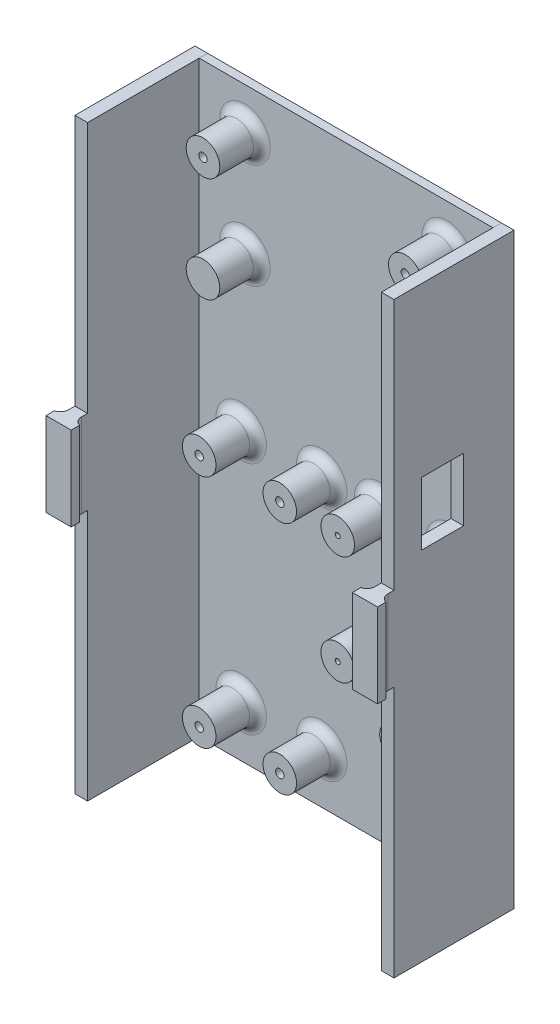
SolidWorks part; units mm, degrees
ref_plane "Přední rovina" through (0, 0, 0) normal (0, 0, 1) x (1, 0, 0)
ref_plane "Horní rovina" through (0, 0, 0) normal (0, 1, 0) x (1, 0, 0)
ref_plane "Pravá rovina" through (0, 0, 0) normal (1, 0, 0) x (0, 0, -1)
sketch "Skica1" plane through (0, 0, 0) normal (0, 0, 1) x (1, 0, 0)
  line L1 (0, 0) -> (70, 0)
  line L2 (0, 0) -> (0, 140)
  line L3 (0, 140) -> (70, 140)
  line L4 (70, 0) -> (70, 140)
  dimension "D1" = 140
  dimension "D2" = 70
extrude "Přidat vysunutím1" add sketch "Skica1" along normal blind 2
sketch "Skica2" plane through (0, 0, 2) normal (0, 0, 1) x (1, 0, 0)
  line L1 (70, 140) -> (0, 140) construction
  line L5 (0, 140) -> (0, 0) construction
  line L9 (70, 0) -> (70, 140) construction
  line L10 (0, 0) -> (70, 0) construction
  circle A0 centre (59.1, 130) radius 1
  circle A1 centre (10.9, 130) radius 1
  circle A2 centre (10, 68) radius 1
  circle A3 centre (29.2, 68) radius 1
  circle A4 centre (10, 12) radius 1
  circle A5 centre (29.2, 12) radius 1
  circle A6 centre (43, 68) radius 0.6
  circle A7 centre (60, 68) radius 0.6
  circle A8 centre (60, 42) radius 0.6
  circle A9 centre (55, 30) radius 0.6
  circle A10 centre (10, 68) radius 4
  circle A11 centre (29.2, 68) radius 4
  circle A12 centre (43, 68) radius 4
  circle A13 centre (60, 68) radius 4
  circle A14 centre (60, 42) radius 4
  circle A15 centre (55, 30) radius 4
  circle A16 centre (29.2, 12) radius 4
  circle A17 centre (10, 12) radius 4
  circle A18 centre (10.9, 130) radius 4
  circle A19 centre (59.1, 130) radius 4
  circle A20 centre (43, 42) radius 0.6
  circle A21 centre (43, 42) radius 4
  circle A22 centre (10.9, 105) radius 4
  circle A23 centre (59.1, 105) radius 4
  circle A24 centre (60, 14) radius 4
  dimension "D1" = 2
  dimension "D2" = 2
  dimension "D3" = 48.2
  dimension "D5" = 10.9
  dimension "D6" = 10
  dimension "D7" = 2
  dimension "D8" = 2
  dimension "D9" = 1.2
  dimension "D10" = 1.2
  dimension "D11" = 1.2
  dimension "D12" = 2
  dimension "D13" = 2
  dimension "D14" = 56
  dimension "D15" = 56
  dimension "D16" = 10
  dimension "D17" = 62
  dimension "D18" = 19.2
  dimension "D19" = 19.2
  dimension "D20" = 10
  dimension "D21" = 12
  dimension "D22" = 26
  dimension "D23" = 0
  dimension "D24" = 17
  dimension "D25" = 10
  dimension "D26" = 62
  dimension "D27" = 42
  dimension "D28" = 30
  dimension "D29" = 1.2
  dimension "D30" = 15
  dimension "D31" = 8
  dimension "D32" = 8
  dimension "D33" = 8
  dimension "D34" = 8
  dimension "D35" = 8
  dimension "D36" = 8
  dimension "D37" = 8
  dimension "D38" = 8
  dimension "D39" = 8
  dimension "D40" = 8
  dimension "D42" = 1.2
  dimension "D43" = 8
  dimension "D44" = 17
  dimension "D45" = 26
  dimension "D46" = 8
  dimension "D47" = 8
  dimension "D48" = 25
  dimension "D49" = 25
  dimension "D50" = 48.2
  dimension "D51" = 10.9
  dimension "D52" = 8
  dimension "D53" = 10
  dimension "D54" = 14
  dimension "D41" = 62
extrude "Přidat vysunutím2" add sketch "Skica2" along normal blind 10
sketch "Skica4" plane through (0, 0, 0) normal (0, 0, 1) x (1, 0, 0)
  line L1 (0, 0) -> (-3, 0)
  line L2 (0, 0) -> (0, 140)
  line L3 (0, 140) -> (-3, 140)
  line L4 (-3, 0) -> (-3, 140)
  line L25 (35, 128.5362) -> (35, -20.7413) construction
  line L34 (73, 0) -> (73, 140)
  line L52 (70, 140) -> (73, 140)
  line L53 (70, 0) -> (70, 140)
  line L54 (70, 0) -> (73, 0)
  dimension "D4" = 140
  dimension "D12" = 35
  dimension "D14" = 3
extrude "Přidat vysunutím3" add sketch "Skica4" along normal blind 32 separate body contours L4 L1 L3 | L52 L54 region at (-1.5, 70, 0) region at (71.5, 70, 0)
sketch "Skica5" plane through (73, 0, 0) normal (1, 0, 0) x (0, 0, -1)
  line L0 (0, 0) -> (0, 140) construction
  line L1 (-22, 85) -> (-12, 85)
  line L2 (-22, 85) -> (-22, 100)
  line L3 (-22, 100) -> (-12, 100)
  line L4 (-12, 85) -> (-12, 100)
  line L5 (-22, 100) -> (-12, 100)
  line L6 (0, 140) -> (-32, 140) construction
  dimension "D1" = 40
  dimension "D2" = 15
  dimension "D3" = 10
  dimension "D4" = 12
extrude "Odebrat vysunutím2" cut sketch "Skica5" against normal blind 20 contours L3 L4 L1 L2
fillet "Zaoblit1" radius 2 14 edges at (6, 12, 2) (25.2, 12, 2) (51, 30, 2) (56, 42, 2) (6.9, 130, 2) (55.1, 130, 2) (56, 68, 2) (39, 68, 2) (25.2, 68, 2) (6, 68, 2) (39, 42, 2) (56, 14, 2) (55.1, 105, 2) (6.9, 105, 2)
sketch "Skica7" plane through (0, 0, 0) normal (0, -1, 0) x (1, 0, 0)
  line L0 (0, 32) -> (0, 0) construction
  line L1 (1.5, 32) -> (-4.5, 32)
  line L2 (1.5, 32) -> (1.5, 34)
  line L3 (1.5, 34) -> (-4.5, 34)
  line L4 (-4.5, 32) -> (-4.5, 34)
  line L10 (35, 57.629) -> (35, -12.1968) construction
  line L11 (74.5, 32) -> (74.5, 34)
  line L12 (68.5, 34) -> (74.5, 34)
  line L13 (68.5, 32) -> (68.5, 34)
  line L14 (68.5, 32) -> (74.5, 32)
  line L15 (0, 0) -> (-3, 0) construction
  dimension "D1" = 1.5
  dimension "D2" = 32
  dimension "D3" = 2
  dimension "D4" = 6
  dimension "D5" = 35
extrude "Přidat vysunutím4" add sketch "Skica7" against normal blind 140
fillet "Zaoblit2" radius 2 2 edges at (-3, 70, 32) (0, 70, 32)
fillet "Zaoblit3" radius 2 2 edges at (73, 70, 32) (70, 70, 32)
sketch "Skica8" plane through (0, 0, 12) normal (0, 0, 1) x (1, 0, 0)
  line L1 (56, 34) -> (65.5, 34)
  line L2 (56, 34) -> (56, 26)
  line L3 (56, 26) -> (65.5, 26)
  line L4 (65.5, 34) -> (65.5, 26)
  line L5 (48, 34) -> (54, 34)
  line L6 (48, 34) -> (48, 26)
  line L7 (48, 26) -> (54, 26)
  line L8 (54, 34) -> (54, 26)
  line L9 (68.5, 140) -> (68.5, 0) construction
  circle A2 centre (55, 30) radius 0.6 construction
  point P8 (54, 30)
  point P10 (0, 0)
  point P11 (0, 0)
  point P14 (60.75, 34)
  point P15 (0, 0)
  point P16 (56, 30)
  point P18 (55, 30)
  point P21 (0, 0)
  dimension "D1" = 8
  dimension "D2" = 1
  dimension "D3" = 1
  dimension "D4" = 8
  dimension "D5" = 3
  dimension "D6" = 6
extrude "Odebrat vysunutím3" cut sketch "Skica8" against normal blind 2
sketch "Skica9" plane through (0, 0, 0) normal (0, -1, 0) x (1, 0, 0)
  line L1 (-10.0634, 38.6) -> (7.9366, 38.6)
  line L2 (-10.0634, 38.6) -> (-10.0634, 28.6)
  line L3 (-10.0634, 28.6) -> (7.9366, 28.6)
  line L4 (7.9366, 38.6) -> (7.9366, 28.6)
  line L5 (62.06, 38.6) -> (80.06, 38.6)
  line L6 (62.06, 38.6) -> (62.06, 28.6)
  line L7 (62.06, 28.6) -> (80.06, 28.6)
  line L8 (80.06, 38.6) -> (80.06, 28.6)
  line L9 (0, 30.0635) -> (0, 0) construction
  line L10 (70, 30.0635) -> (70, 0) construction
  line L11 (0, 2) -> (70, 2) construction
  dimension "D1" = 10
  dimension "D2" = 18
  dimension "D3" = 26.6
  dimension "D4" = 7.9366
  dimension "D5" = 7.94
  dimension "D6" = 18
  dimension "D7" = 10
  dimension "D8" = 26.6
extrude "Odebrat vysunutím4" cut sketch "Skica9" against normal blind 60
sketch "Skica10" plane through (0, 140, 0) normal (0, 1, 0) x (1, 0, 0)
  line L0 (70, -2) -> (0, -2) construction
  line L1 (-10.06, -28.6) -> (7.94, -28.6)
  line L2 (-10.06, -28.6) -> (-10.06, -38.6)
  line L3 (-10.06, -38.6) -> (7.94, -38.6)
  line L4 (7.94, -28.6) -> (7.94, -38.6)
  line L5 (0, -30.0635) -> (0, 0) construction
  line L6 (70, -30.0635) -> (70, 0) construction
  line L7 (62.06, -28.6) -> (80.06, -28.6)
  line L8 (62.06, -28.6) -> (62.06, -38.6)
  line L9 (62.06, -38.6) -> (80.06, -38.6)
  line L10 (80.06, -28.6) -> (80.06, -38.6)
  dimension "D1" = 26.6
  dimension "D2" = 10
  dimension "D3" = 18
  dimension "D4" = 7.94
  dimension "D5" = 7.94
  dimension "D6" = 10
  dimension "D7" = 18
  dimension "D8" = 26.6
extrude "Odebrat vysunutím5" cut sketch "Skica10" against normal blind 60
